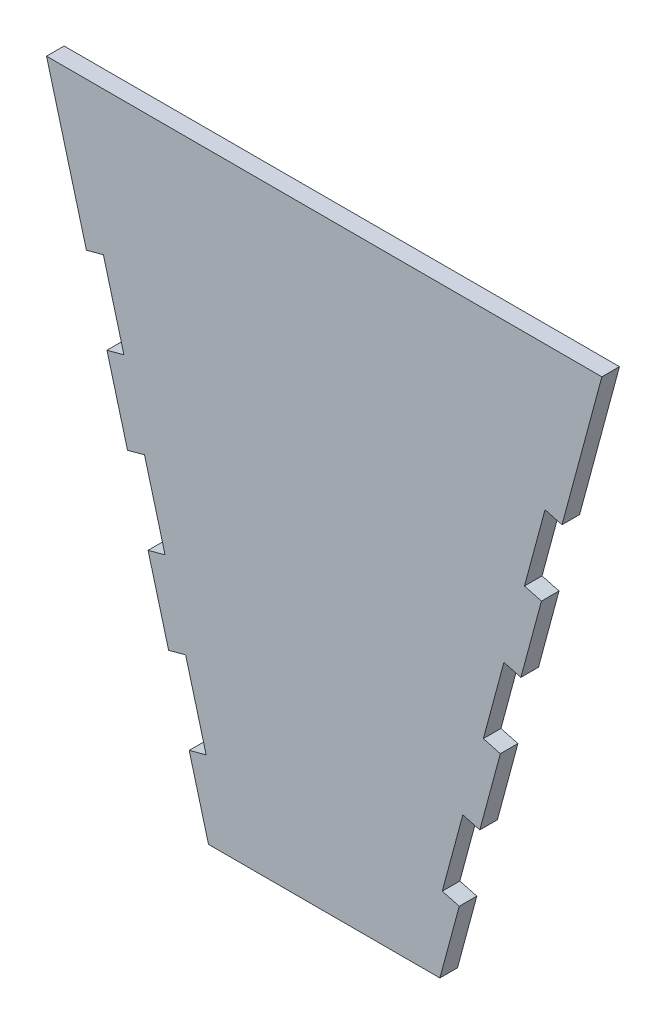
SolidWorks part; units mm, degrees
ref_plane "Front Plane" through (0, 0, 0) normal (0, 0, 1) x (1, 0, 0)
ref_plane "Top Plane" through (0, 0, 0) normal (0, 1, 0) x (1, 0, 0)
ref_plane "Right Plane" through (0, 0, 0) normal (1, 0, 0) x (0, 0, -1)
sketch "Sketch1" plane through (0, 0, 0) normal (0, 0, 1) x (1, 0, 0)
  line L0 (0, 165.1) -> (44.45, 0)
  line L1 (0, 0) -> (152.4, 0)
  line L2 (0, 0) -> (0, 165.1)
  line L3 (0, 165.1) -> (152.4, 165.1)
  line L4 (152.4, 0) -> (152.4, 165.1)
  line L6 (152.4, 165.1) -> (107.95, 0)
  dimension "D1" = 152.4
  dimension "D2" = 165.1
  dimension "D3" = 44.45
  dimension "D4" = 44.45
extrude "Boss-Extrude1" add sketch "Sketch1" along normal blind 4.826 contours L6 L3 L0 L1 region at (76.2, 93.8804, 0)
sketch "Sketch2" plane through (0, 0, 4.826) normal (0, 0, 1) x (1, 0, 0)
  line L0 (76.2, 0) -> (76.2, 165.1) construction
  line L1 (10.9436, 124.4523) -> (15.6037, 125.7069)
  line L2 (0, 165.1) -> (44.45, 0) construction
  line L3 (15.6037, 125.7069) -> (21.2444, 104.7558)
  line L4 (21.2444, 104.7558) -> (16.5843, 103.5012)
  line L5 (16.5843, 103.5012) -> (10.9436, 124.4523)
  line L6 (22.225, 82.55) -> (26.8851, 83.8046)
  line L7 (26.8851, 83.8046) -> (32.5258, 62.8535)
  line L8 (32.5258, 62.8535) -> (27.8657, 61.5988)
  line L9 (27.8657, 61.5988) -> (22.225, 82.55)
  line L10 (33.5064, 40.6477) -> (38.1665, 41.9023)
  line L11 (38.1665, 41.9023) -> (43.8072, 20.9512)
  line L12 (43.8072, 20.9512) -> (39.1471, 19.6965)
  line L13 (39.1471, 19.6965) -> (33.5064, 40.6477)
  line L14 (0, 165.1) -> (152.4, 165.1) construction
  line L16 (21.2444, 104.7558) -> (26.8851, 83.8046) construction
  line L17 (32.5258, 62.8535) -> (38.1665, 41.9023) construction
  line L18 (43.8072, 20.9512) -> (49.4478, 0) construction
  line L19 (44.45, 0) -> (107.95, 0) construction
  line L20 (108.5928, 20.9512) -> (102.9522, 0) construction
  line L21 (119.8742, 62.8535) -> (114.2335, 41.9023) construction
  line L22 (131.1556, 104.7558) -> (125.5149, 83.8046) construction
  line L23 (113.2529, 19.6965) -> (118.8936, 40.6477)
  line L24 (108.5928, 20.9512) -> (113.2529, 19.6965)
  line L25 (114.2335, 41.9023) -> (108.5928, 20.9512)
  line L26 (118.8936, 40.6477) -> (114.2335, 41.9023)
  line L27 (124.5343, 61.5988) -> (130.175, 82.55)
  line L28 (119.8742, 62.8535) -> (124.5343, 61.5988)
  line L29 (125.5149, 83.8046) -> (119.8742, 62.8535)
  line L30 (130.175, 82.55) -> (125.5149, 83.8046)
  line L31 (135.8157, 103.5012) -> (141.4564, 124.4523)
  line L32 (131.1556, 104.7558) -> (135.8157, 103.5012)
  line L33 (136.7963, 125.7069) -> (131.1556, 104.7558)
  line L34 (141.4564, 124.4523) -> (136.7963, 125.7069)
  line L35 (43.8072, 20.9512) -> (49.4478, 0) construction
  dimension "D1" = 4.826
extrude "Cut-Extrude1" cut sketch "Sketch2" against normal through all
equation "\"MDF\"= 0.19in"
equation "\"PVCID\" = 2.067in"
equation "\"PVCOD\" = 2.375in"
equation "\"GenDiameter\"= 60mm"
equation "\"GenCutDiameter\" = 1.8in"
equation "\"GenCutDistance\" = 1"
equation "\"TowerHeight\" = 6in"
equation "\"TowerFrontBase\" = 3in"
equation "\"FunnelHeight\" = 1in"
equation "\"FunnelAngle\" = 20"
equation "\"TowerSideBase\" = 3in"
equation "\"TowerPanelLength\" = 2in"
equation "\"TowerPanelLeeway\" = 0.5in"
equation "\"BaseLength\" = 9in"
equation "\"BaseWidth\" = 10in"
equation "\"WheelHoleLength\" = 3.25in"
equation "\"WheelHoleWidth\" = 26mm"
equation "\"WheelHoleFromBack\" = 1.5in"
equation "\"DropLength\" = 1in"
equation "\"DropWidth\" = 8.5in"
equation "\"BumperWidth\" = 1in"
equation "\"SmallHexDiameter\" = 0.185in"
equation "\"SmallHexHeight\" = 0.701in"
equation "\"ScrewSize\" = 0.106in"
equation "\"BigHexDiameter\" = 0.251in"
equation "\"BigHexHeight\" = 0.374in"
equation "\"PCBThickness\" = 0.066in"
equation "\"ConnectorHeight\" = 0.517in"
equation "\"BoardHeight\" = 0.583in"
equation "\"UnoStackHeight\" = 1.351in"
equation "\"UnoStackWidth\" = 3.053in"
equation "\"UnoStackLength\" = 3.152in"
equation "\"HBridgeWidth\" = 1.797in"
equation "\"HBridgeLength\" = 2.236in"
equation "\"DSWidth\" = 1.820in"
equation "\"DSLength\" = 1.833in"
equation "\"StepperWidth\" = 1.799in"
equation "\"StepperLength\" = 2.248in"
equation "\"ULNWidth\" = 1.304in"
equation "\"ULNLength\" = 1.545in"
equation "\"VSwitchHeight\" = 0.392in"
equation "\"VSwitchWidth\" = 0.637in"
equation "\"VSwitchLength\" = 1.097in"
equation "\"SkateWheelDiameter\" = 80mm"
equation "\"SkateWheelThickness\" = 24mm"
equation "\"BaseDistance\" = 3in"
equation "\"DummyVar\" = 2in"
equation "\"D1@Boss-Extrude1\"=\"MDF\""
equation "\"D1@Sketch2\"=\"MDF\""
